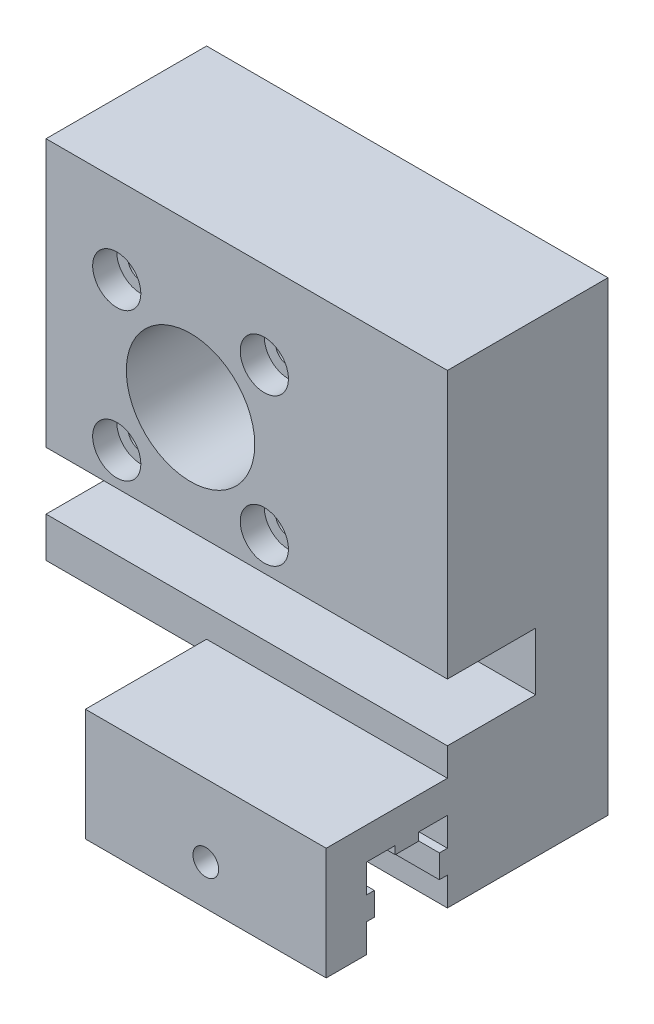
SolidWorks part; units mm, degrees
ref_plane "Front Plane" through (0, 0, 0) normal (0, 0, 1) x (1, 0, 0)
ref_plane "Top Plane" through (0, 0, 0) normal (0, 1, 0) x (1, 0, 0)
ref_plane "Right Plane" through (0, 0, 0) normal (1, 0, 0) x (0, 0, -1)
sketch "Esquisse1" plane through (0, 0, 0) normal (0, 0, 1) x (1, 0, 0)
  line L0 (25, 22.5) -> (25, -22.5)
  line L1 (-25, 22.5) -> (25, 22.5)
  line L2 (-25, 22.5) -> (-25, -22.5)
  line L3 (-25, -22.5) -> (25, -22.5)
  point P4 (-25, 0)
  point P6 (0, -22.5)
  dimension "D3" = 45
  dimension "D4" = 50
extrude "Main Extrusion" add sketch "Esquisse1" along normal blind 20
sketch "Esquisse5" plane through (0, 0, 20) normal (0, 0, 1) x (1, 0, 0)
  line L1 (-25, -22.5) -> (25, -22.5) construction
  line L3 (-25, 22.5) -> (-25, -22.5) construction
  circle A0 centre (-7, 2.5) radius 8
  dimension "D1" = 16
  dimension "D2" = 25
  dimension "D3" = 18
extrude "Gear Linear Holes" cut sketch "Esquisse5" against normal through all
sketch "Esquisse8" plane through (0, 0, 0) normal (1, 0, 0) x (0, 0, -1)
  line L0 (-20, -25.5) -> (-20, -29.05)
  line L1 (-20, -25.5) -> (-23.6, -25.5)
  line L2 (-23.6, -25.5) -> (-23.6, -26.5)
  line L3 (-23.6, -26.5) -> (-26.5, -26.5)
  line L4 (-26.5, -26.5) -> (-26.5, -25.5)
  line L5 (-35.1, -21.5) -> (0, -21.5)
  line L6 (-20, -35.5) -> (0, -35.5)
  line L7 (0, -35.5) -> (0, -21.5)
  line L8 (0, -22.5) -> (0, 22.5) construction
  line L9 (-26.5, -25.5) -> (-30.1, -25.5)
  line L10 (-20, -22.5) -> (0, -22.5) construction
  line L12 (0, 22.5) -> (0, -22.5) construction
  line L13 (-30.1, -25.5) -> (-30.1, -29.05)
  line L14 (-30.1, -35.5) -> (-35.1, -35.5)
  line L15 (-35.1, -35.5) -> (-35.1, -21.5)
  line L16 (-20, -29.05) -> (-21, -29.05)
  line L17 (-21, -29.05) -> (-21, -31.95)
  line L18 (-21, -31.95) -> (-20, -31.95)
  line L19 (-20, -31.95) -> (-20, -35.5)
  line L21 (-30.1, -29.05) -> (-29.1, -29.05)
  line L22 (-29.1, -29.05) -> (-29.1, -31.95)
  line L23 (-29.1, -31.95) -> (-30.1, -31.95)
  line L24 (-30.1, -31.95) -> (-30.1, -35.5)
  line L25 (-20, 22.5) -> (-20, -22.5) construction
  dimension "D1" = 2.9
  dimension "D2" = 10.1
  dimension "D3" = 1
  dimension "D4" = 3
  dimension "D5" = 10
  dimension "D6" = 5
  dimension "D7" = 4
extrude "Fixing Extrusion" add sketch "Esquisse8" along normal mid plane 50
sketch "Esquisse12" plane through (0, 0, 0) normal (0, 0, 1) x (1, 0, 0)
  circle A0 centre (-7, 2.5) radius 16
  dimension "D1" = 32
sketch "Esquisse13" plane through (0, 0, 20) normal (0, 0, 1) x (1, 0, 0)
  line L0 (-25, 22.5) -> (-25, -21.5) construction
  line L1 (-25, -18) -> (25, -18)
  line L2 (-25, -18) -> (-25, -10.8)
  line L3 (-25, -10.8) -> (25, -10.8)
  line L4 (25, -18) -> (25, -10.8)
  line L5 (25, -21.5) -> (25, 22.5) construction
  line L7 (-25, -21.5) -> (25, -21.5) construction
  dimension "D1" = 3.5
  dimension "D2" = 7.2
extrude "RollingBallHorizontalHole" cut sketch "Esquisse13" against normal blind 11
sketch "Esquisse14" plane through (-25, 0, 0) normal (-1, 0, 0) x (0, 0, 1)
  line L0 (0, -23) -> (20, -23)
  line L1 (0, -35.5) -> (35.1, -35.5)
  line L2 (0, -35.5) -> (0, -23)
  line L3 (20, -23) -> (20, -18)
  line L4 (35.1, -35.5) -> (35.1, -18)
  line L5 (20, -18) -> (35.1, -18)
  line L6 (20, -18) -> (20, -21.5) construction
  dimension "D1" = 12.5
extrude "FrontHole" cut sketch "Esquisse14" against normal blind 20
sketch "Esquisse15" plane through (0, 0, 35.1) normal (0, 0, 1) x (1, 0, 0)
  line L1 (25, -21.5) -> (25, -35.5) construction
  line L4 (-5, -31.95) -> (-5, -29.05) construction
  circle A1 centre (10, -30.5) radius 1.6
  point P5 (-5, -30.5)
  dimension "D1" = 3.2
  dimension "D2" = 15
extrude "BottomFixingHole" cut sketch "Esquisse15" against normal through all
extrude "ReductorMainHole" cut sketch "Esquisse12" along normal blind 5
sketch "Esquisse16" plane through (0, 0, 5) normal (0, 0, -1) x (-1, 0, 0)
  line L0 (2.6411, 11.5) -> (11.3589, 11.5)
  line L1 (2.6411, -6.5) -> (11.3589, -6.5)
  arc A0 (2.6411, 11.5) -> (2.6411, -6.5) centre (7, 2.5) ccw
  arc A2 (11.3589, 11.5) -> (11.3589, -6.5) centre (7, 2.5) cw
  circle A3 centre (7, 2.5) radius 16 construction
  dimension "D1" = 10
  dimension "D2" = 18
extrude "ReductorFrontFixingHole" cut sketch "Esquisse16" against normal blind 3
sketch "Esquisse17" plane through (0, 0, 5) normal (0, 0, -1) x (-1, 0, 0)
  line L0 (7, 2.5) -> (-2.1924, 11.6924) construction
  line L1 (11, 0) -> (-11, 0) construction
  line L2 (-2.1924, -6.6924) -> (16.1924, 11.6924) construction
  line L3 (7, 2.5) -> (16.1924, -6.6924) construction
  circle A0 centre (-2.1924, 11.6924) radius 1.6
  circle A1 centre (16.1924, 11.6924) radius 1.6
  circle A2 centre (-2.1924, -6.6924) radius 1.6
  circle A3 centre (16.1924, -6.6924) radius 1.6
  point P7 (16.1924, 11.6924)
  point P13 (-2.1924, -6.6924)
  point P14 (16.1924, 11.6924)
  dimension "D1" = 3.2
  dimension "D2" = 45
  dimension "D3" = 13
  dimension "D4" = 13
  dimension "D5" = 13
extrude "MotorFixingHole" cut sketch "Esquisse17" against normal through all
sketch "Esquisse19" plane through (0, 0, 20) normal (0, 0, 1) x (1, 0, 0)
  circle A0 centre (-16.1924, 11.6924) radius 3
  circle A1 centre (2.1924, 11.6924) radius 3
  circle A2 centre (-16.1924, -6.6924) radius 3
  circle A3 centre (2.1924, -6.6924) radius 3
  dimension "D1" = 6
extrude "Enlèv. mat.-Extru.5" cut sketch "Esquisse19" against normal blind 3
